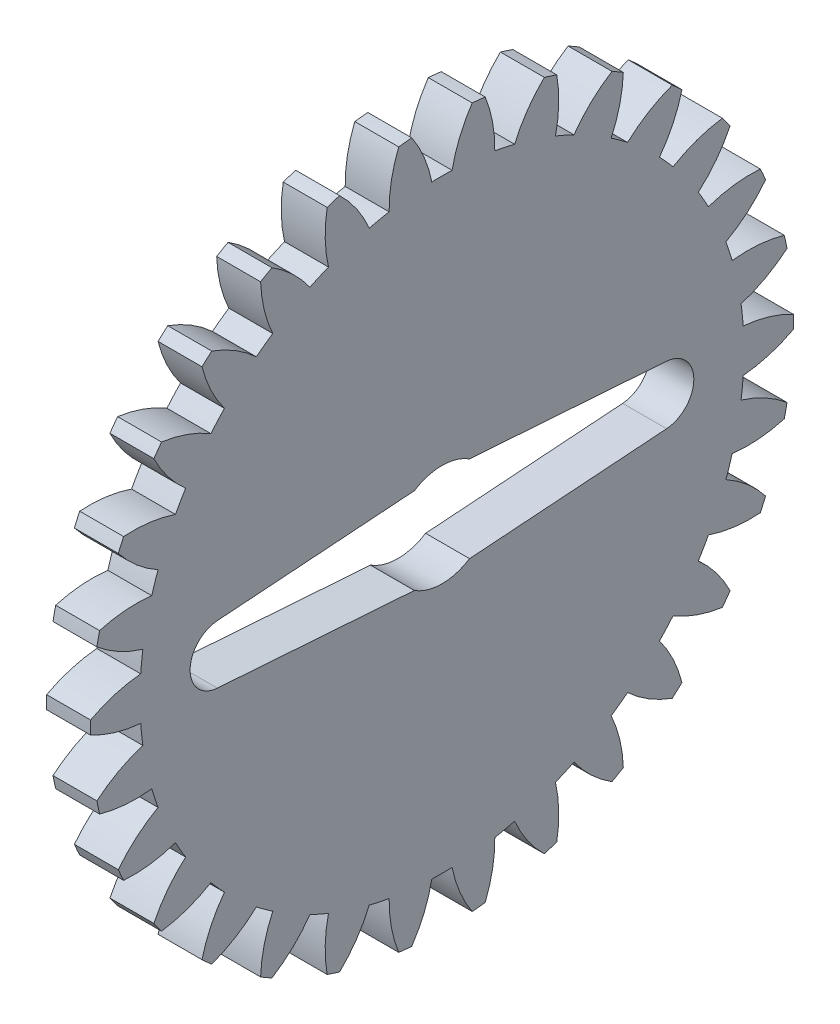
SolidWorks part; units mm, degrees
material "Acrylic (Medium-high impact)"
ref_plane "Plane1" through (0, 0, 0) normal (0, 0, 1) x (1, 0, 0)
ref_plane "Plane2" through (0, 0, 0) normal (0, 1, 0) x (1, 0, 0)
ref_plane "Plane3" through (0, 0, 0) normal (1, 0, 0) x (0, 0, -1)
other "Configuration Table"
sketch "HoldingSke" plane through (0, 0, 0) normal (0, 1, 0) x (1, 0, 0)
  line L0 (0, 0) -> (57.735, -33.3333)
  line L1 (-15, 0) -> (100, 0) construction
  line L2 (0, 0) -> (-2.1039, 2.3779)
  line L3 (0, 0) -> (-11.863, 4.5341)
  line L4 (0, 0) -> (7.479, 4.318)
  line L5 (0, 0) -> (-46.8476, -17.4728)
  line L6 (0, 0) -> (-4.1448, -2.7965)
  line L7 (-2.1039, 2.3779) -> (8.6588, 51.2068)
  line L8 (-76.2, 54.61) -> (-75.5, 54.61)
  line L9 (-71.009, 38.7566) -> (-53.1078, 45.2721)
  line L10 (-76.2, 71.12) -> (104.1128, 71.12)
  line L11 (0, 0) -> (-5, 0)
  line L12 (-76.2, 101.6) -> (-76.147, 101.6)
  line L13 (24.9733, 27.94) -> (52.9518, 28.4284)
  line L14 (24.9733, 27.94) -> (24.9743, 27.94)
  line L15 (24.9733, 27.94) -> (100.4006, 29.5858)
  line L16 (-63.627, -1.5) -> (-12.827, -1.5)
  circle A0 centre (0, 0) radius 2
  circle A1 centre (0, 0) radius 20.624
  circle A2 centre (0, 0) radius 37.5
  circle A3 centre (0, 0) radius 2
  dimension "MHD" = 41.248
  dimension "Hub_dia" = 75
  dimension "Bore" = 4
  dimension "MBD" = 4
  dimension "Num_teeth" = 30
  dimension "Pitch" = 66.6667
  dimension "Overall_len" = 50
  dimension "Show_teeth" = 30
  dimension "Thickness" = 5
  dimension "OAL" = 50.001
  dimension "T_dim" = 0.7
  dimension "Ap" = 20
  dimension "H" = 19.05
  dimension "Pitch_radius" = 180.3128
  dimension "Width" = 5
  dimension "Backlash" = 0.053
  dimension "Addendum_fac" = 1
  dimension "Dedendum_fac" = 1.25
  dimension "Clearance_fac" = 0.25
  dimension "Dedendum_add" = 0.001
  dimension "Module" = 1.5
sketch "BasProSke" plane through (0, 0, 0) normal (0, 1, 0) x (1, 0, 0)
  line L0 (-10, 0) -> (60, 0) construction
  line L1 (0, 0) -> (0, 24)
  line L2 (0, 0) -> (3, 0)
  line L3 (3, 0) -> (3, 24)
  line L4 (3, 24) -> (0, 24)
  dimension "Diameter" = 48
  dimension "D1" = 3
revolve "Base-Revolve" add sketch "BasProSke" angle 360 about L0
sketch "TooCutSke" plane through (0, 0, 0) normal (1, 0, 0) x (0, 0, -1)
  line L1 (0, 0) -> (0, 107) construction
  line L2 (0, 0) -> (-1.2703, 22.4641) construction
  line L3 (0, 0) -> (-4.6983, 44.7014) construction
  line L4 (-1.2703, 22.4641) -> (-2.3492, 22.3507) construction
  arc A0 (0.6933, 20.6123) -> (-0.6933, 20.6123) centre (0, 0) ccw
  arc A1 (2.232, 24.1511) -> (-2.232, 24.1511) centre (0, 0) ccw
  circle A2 centre (0, 0) radius 22.5 construction
  circle A3 centre (0, 0) radius 21.1431 construction
  arc A4 (-0.6933, 20.6123) -> (-2.232, 24.1511) centre (-9.5243, 18.8764) ccw
  arc A5 (2.232, 24.1511) -> (0.6933, 20.6123) centre (9.5243, 18.8764) ccw
  dimension "Root_dia" = 41.248
  dimension "Overcut_dia" = 48.508
  dimension "Pitch_dia" = 45
  dimension "Base_dia" = 42.2862
  dimension "Flank_rad" = 9
  dimension "Half_ang" = 6
  dimension "Half_CT" = 1.0848
extrude "ToothCut" cut sketch "TooCutSke" along normal through all
fillet "Breaks" [suppressed] radius 0.03 tangent propagation no
fillet "RootFillets" [suppressed] radius 0.376
pattern_circular "TeethCuts" count 30 every 12 about axis through (-10, 0, 0) along (1, 0, 0) of "ToothCut", "RootFillets", "Breaks"
sketch "HubNeaOneSke" plane through (0, 0, 0) normal (-1, 0, 0) x (0, 0, 1)
  circle A0 centre (0, 0) radius 20.624
  dimension "Diameter" = 41.248
extrude "HubNearOne" [suppressed] add sketch "HubNeaOneSke" along normal blind 45.0005
sketch "HubNeaBotSke" plane through (0, 0, 0) normal (-1, 0, 0) x (0, 0, 1)
  circle A0 centre (0, 0) radius 20.624
  dimension "Diameter" = 41.248
extrude "HubNearBoth" [suppressed] add sketch "HubNeaBotSke" along normal blind 22.5003
ref_plane "FarPln" through (5, 0, 0) normal (1, 0, 0) x (0, 0, -1)
sketch "HubFarSke" plane through (5, 0, 0) normal (1, 0, 0) x (0, 0, -1)
  circle A0 centre (0, 0) radius 20.624
  dimension "Diameter" = 41.248
extrude "HubFar" [suppressed] add sketch "HubFarSke" along normal blind 22.5003
sketch "BorSke" plane through (0, 0, 0) normal (1, 0, 0) x (0, 0, -1)
  circle A0 centre (0, 0) radius 2
  dimension "Diameter" = 4
extrude "Bore" cut sketch "BorSke" along normal mid plane 100.002
sketch "KeySke" plane through (0, 0, 0) normal (1, 0, 0) x (0, 0, -1)
  line L0 (-0.8, 0) -> (-0.8, 2.7)
  line L1 (-0.8, 2.7) -> (0.8, 2.7)
  line L2 (0.8, 2.7) -> (0.8, 0)
  line L3 (0, 0) -> (0, 34) construction
  line L4 (-0.8, 0) -> (0.8, 0)
  dimension "Offset" = 2.7
  dimension "Width" = 1.6
extrude "Keyway" [suppressed] cut sketch "KeySke" along normal mid plane 100.002
pattern_circular "Keyway2" [suppressed] count 2 every 90 about axis through (-10, 0, 0) along (1, 0, 0) reverse direction yes
sketch "Sketch2" plane through (0, 0, 0) normal (-1, 0, 0) x (0, 0, 1)
  line L2 (0, 3.3151) -> (0, -3.3151) construction
  line L5 (-1.8835, 2.95) -> (-15.3416, 1.995)
  line L6 (-15.3416, -1.995) -> (-1.8835, -2.95)
  line L7 (15.3416, -1.995) -> (1.8835, -2.95)
  line L8 (1.8835, 2.95) -> (15.3416, 1.995)
  arc A2 (-1.8835, -2.95) -> (1.8835, -2.95) centre (0, 0) ccw
  arc A3 (-15.3416, 1.995) -> (-15.3416, -1.995) centre (-15.2, 0) ccw
  arc A5 (15.3416, 1.995) -> (15.3416, -1.995) centre (15.2, 0) cw
  arc A7 (-15.3416, -1.995) -> (-15.3416, 1.995) centre (-15.2, 0) ccw construction
  arc A8 (-1.8835, 2.95) -> (-1.8835, -2.95) centre (0, 0) ccw construction
  arc A9 (1.8835, -2.95) -> (1.8835, 2.95) centre (0, 0) ccw construction
  arc A10 (1.8835, 2.95) -> (-1.8835, 2.95) centre (0, 0) ccw
  arc A11 (15.3416, -1.995) -> (15.3416, 1.995) centre (15.2, 0) cw construction
  dimension "D1" = 7
  dimension "D2" = 4
  dimension "D3" = 5.9
  dimension "D4" = 15.2
extrude "Cut-Extrude1" cut sketch "Sketch2" against normal through all
equation "' \"Module@HoldingSke\" = 6.35"
equation "' \"Num_teeth@HoldingSke\" = 12"
equation "' \"Ap@HoldingSke\" =  20"
equation "' \"Ap@HoldingSke\" = 20"
equation "' \"Width@HoldingSke\" = 0.5 * 25.4"
equation "' \"Hub_dia@HoldingSke\"= 1 * 25.4"
equation "' \"Hub_dia@HoldingSke\" = 1 * 25.4"
equation "' \"Overall_len@HoldingSke\" = 1.0 * 25.4"
equation "' \"Bore@HoldingSke\" = 0.75 * 25.4"
equation "' \"T_dim@HoldingSke\" = 0.1 * 25.4"
equation "' \"Width@KeySke\" = 0.25 * 25.4"
equation "' \"Show_teeth@HoldingSke\" = 13"
equation "' \"Backlash@HoldingSke\" = 0.009 * 25.4"
equation "' \"Addendum_fac@HoldingSke\" = 1.0"
equation "' \"Dedendum_fac@HoldingSke\" = 1.25"
equation "' \"Dedendum_add@HoldingSke\" = 0.00005 * 25.4"
equation "' \"Clearance_fac@HoldingSke\" = 0.25"
equation "\"Pitch@HoldingSke\" = 1 / \"Module@HoldingSke\""
equation "\"Overcut_dia@TooCutSke\" = (\"Num_teeth@HoldingSke\" + 2 * \"Addendum_fac@HoldingSke\") / \"Pitch@HoldingSke\" + 0.002 * 25.4"
equation "\"Pitch_dia@TooCutSke\" = \"Num_teeth@HoldingSke\" / \"Pitch@HoldingSke\""
equation "\"Base_dia@TooCutSke\" = \"Num_teeth@HoldingSke\" / \"Pitch@HoldingSke\" * cos((\"Ap@HoldingSke\"  * 3.14159265 / 180))"
equation "\"Root_dia@TooCutSke\" = (\"Num_teeth@HoldingSke\" + 2) / \"Pitch@HoldingSke\" - 2 * (\"Addendum_fac@HoldingSke\" + \"Dedendum_fac@HoldingSke\") / \"Pitch@HoldingSke\" - \"Dedendum_add@HoldingSke\" * 2"
equation "\"Half_ang@TooCutSke\" = 180 / \"Num_teeth@HoldingSke\""
equation "\"Half_CT@TooCutSke\" = \"Num_teeth@HoldingSke\" / \"Pitch@HoldingSke\" * sin((3.14159265 / 2 / \"Num_teeth@HoldingSke\")) / 2 - 7 * \"Backlash@HoldingSke\" / 4"
equation "\"Flank_rad@TooCutSke\" = \"Num_teeth@HoldingSke\" / \"Pitch@HoldingSke\" / 5"
equation "\"Radius@RootFillets\" = \"Clearance_fac@HoldingSke\" / \"Pitch@HoldingSke\" + \"Dedendum_add@HoldingSke\""
equation "\"Break_rad@Breaks\" = 0.02 / \"Pitch@HoldingSke\""
equation "\"Thickness@HoldingSke\" = \"Width@HoldingSke\""
equation "\"OAL@HoldingSke\" = \"Thickness@HoldingSke\""
equation "\"MHD@HoldingSke\" = (\"Num_teeth@HoldingSke\" + 2) / \"Pitch@HoldingSke\" - 2 * (\"Addendum_fac@HoldingSke\" + \"Dedendum_fac@HoldingSke\")  / \"Pitch@HoldingSke\" - \"Dedendum_add@HoldingSke\" * 2"
equation "\"MBD@HoldingSke\" = (\"Num_teeth@HoldingSke\" + 2) / \"Pitch@HoldingSke\" - 2 * (\"Addendum_fac@HoldingSke\" + \"Dedendum_fac@HoldingSke\")  / \"Pitch@HoldingSke\" - \"Dedendum_add@HoldingSke\" * 2 - 0.002 * 25.4"
equation "\"MHD@HoldingSke\" = ((sgn( \"MHD@HoldingSke\" - \"Hub_dia@HoldingSke\" )-1)*( \"MHD@HoldingSke\" - \"Hub_dia@HoldingSke\" ))/-2+ \"Hub_dia@HoldingSke\""
equation "\"MBD@HoldingSke\" = ((sgn( \"MBD@HoldingSke\" - \"Bore@HoldingSke\" )-1)*( \"MBD@HoldingSke\" - \"Bore@HoldingSke\" ))/-2+ \"Bore@HoldingSke\""
equation "\"OAL@HoldingSke\" = ((sgn( \"OAL@HoldingSke\" - \"Overall_len@HoldingSke\" )+1)*( \"OAL@HoldingSke\" - \"Overall_len@HoldingSke\" ))/2 + \"Overall_len@HoldingSke\" + 0.000002 * 25.4"
equation "\"Num_teeth@TeethCuts\" = int( \"Show_teeth@HoldingSke\" ) + 1"
equation "\"Num_teeth@TeethCuts\" = ((sgn( \"Num_teeth@TeethCuts\" - \"Num_teeth@HoldingSke\" )-1)*( \"Num_teeth@TeethCuts\" - \"Num_teeth@HoldingSke\" ))/-2+ \"Num_teeth@HoldingSke\""
equation "\"Num_teeth@TeethCuts\" = ((sgn( \"Num_teeth@TeethCuts\" - 2.0)+1)*( \"Num_teeth@TeethCuts\" - 2.0))/2 +2.0"
equation "\"Angle@TeethCuts\" = 360.0 / \"Num_teeth@HoldingSke\""
equation "\"Diameter@BasProSke\" = (\"Num_teeth@HoldingSke\" + 2 * \"Addendum_fac@HoldingSke\") / \"Pitch@HoldingSke\""
equation "' \"Fillet_rad@BasProSke\" =  \"Thickness@HoldingSke\" * 0.05"
equation "' \"Fillet_rad@BasProSke\" = \"Thickness@HoldingSke\" * 0.05"
equation "\"MHD@HoldingSke\" = ((sgn( \"MHD@HoldingSke\" - \"Root_dia@TooCutSke\" )-1)*( \"MHD@HoldingSke\" - \"Root_dia@TooCutSke\" ))/-2+ \"Root_dia@TooCutSke\""
equation "\"Diameter@HubNeaOneSke\" = \"MHD@HoldingSke\""
equation "\"Diameter@HubNeaBotSke\" = \"MHD@HoldingSke\""
equation "\"Diameter@HubFarSke\" = \"MHD@HoldingSke\""
equation "\"Diameter@BorSke\" = \"MBD@HoldingSke\""
equation "\"D1@Bore\" = \"OAL@HoldingSke\" * 2.0"
equation "\"D1@Keyway\" = \"OAL@HoldingSke\" * 2.0"
equation "\"Offset@KeySke\" = \"T_dim@HoldingSke\" + \"MBD@HoldingSke\" / 2.0"
